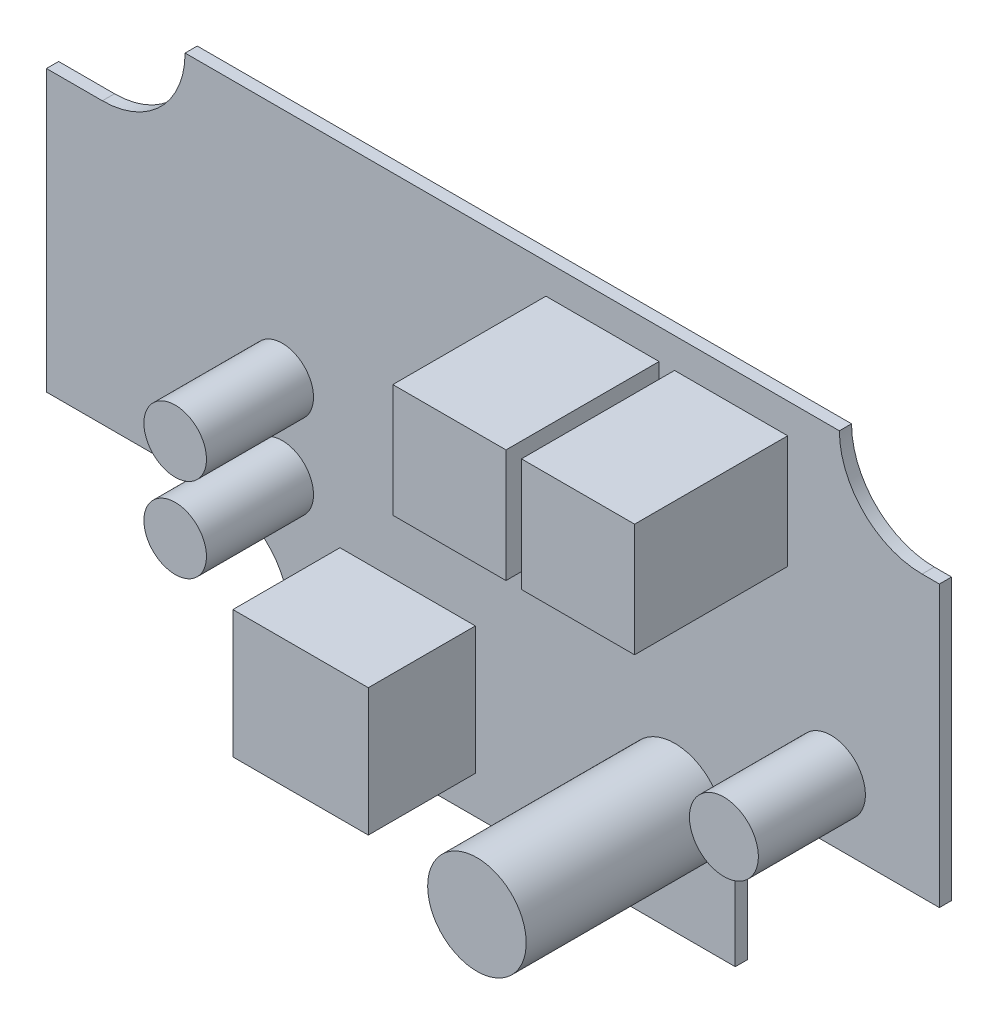
SolidWorks part; units mm, degrees
ref_plane "Front Plane" through (0, 0, 0) normal (0, 0, 1) x (1, 0, 0)
ref_plane "Top Plane" through (0, 0, 0) normal (0, 1, 0) x (1, 0, 0)
ref_plane "Right Plane" through (0, 0, 0) normal (1, 0, 0) x (0, 0, -1)
sketch "Sketch1" plane through (0, 0, 0) normal (0, 0, 1) x (1, 0, 0)
  line L0 (-42.3541, 30.2967) -> (-53.0616, 30.2967) construction
  line L1 (28.8728, -26.0779) -> (28.8728, -36.5363)
  line L2 (-38.257, -16.6937) -> (-60.3013, -16.6937)
  line L3 (-42.3541, 30.2967) -> (42.3541, 30.2967)
  line L4 (38.257, -16.6937) -> (55.3008, -16.6937)
  line L5 (-53.0616, 30.2967) -> (-53.0616, 19.5893) construction
  line L6 (-38.257, -16.6937) -> (-38.257, -26.0779) construction
  line L7 (-38.257, -26.0779) -> (-28.8728, -26.0779) construction
  line L8 (28.8728, -26.0779) -> (38.257, -26.0779) construction
  line L9 (38.257, -26.0779) -> (38.257, -16.6937) construction
  line L10 (53.0616, 19.5893) -> (53.0616, 30.2967) construction
  line L11 (53.0616, 30.2967) -> (42.3541, 30.2967) construction
  line L12 (55.3008, -16.6937) -> (55.3008, 19.5893)
  line L13 (-60.3013, -16.6937) -> (-60.3013, 19.5893)
  line L14 (-60.3013, 19.5893) -> (-53.0616, 19.5893)
  line L15 (55.3008, 19.5893) -> (53.0616, 19.5893)
  line L16 (28.8728, -36.5363) -> (-28.8728, -36.5363)
  line L17 (-28.8728, -36.5363) -> (-28.8728, -26.0779)
  line L21 (0, -36.5363) -> (0, 0) construction
  arc A0 (-42.3541, 30.2967) -> (-53.0616, 19.5893) centre (-53.0616, 30.2967) cw
  arc A2 (-38.257, -16.6937) -> (-28.8728, -26.0779) centre (-38.257, -26.0779) cw
  arc A4 (42.3541, 30.2967) -> (53.0616, 19.5893) centre (53.0616, 30.2967) ccw
  arc A5 (38.257, -16.6937) -> (28.8728, -26.0779) centre (38.257, -26.0779) ccw
  dimension "D1" = 36.2829
  dimension "D2" = 9.3842
  dimension "D3" = 10.7075
  dimension "D4" = 57.7457
  dimension "D5" = 22.0442
  dimension "D6" = 10.4584
  dimension "D7" = 17.0438
  dimension "D8" = 2.2392
extrude "Boss-Extrude1" add sketch "Sketch1" along normal blind 1.5748
sketch "Sketch2" plane through (0, 0, 1.5748) normal (0, 0, 1) x (1, 0, 0)
  line L1 (4.3619, 26.3914) -> (19.0119, 26.3914)
  line L2 (4.3619, 26.3914) -> (4.3619, 11.7414)
  line L3 (4.3619, 11.7414) -> (19.0119, 11.7414)
  line L4 (19.0119, 26.3914) -> (19.0119, 11.7414)
  line L5 (21.0119, 26.3914) -> (35.6619, 26.3914)
  line L6 (21.0119, 26.3914) -> (21.0119, 11.7414)
  line L7 (21.0119, 11.7414) -> (35.6619, 11.7414)
  line L8 (35.6619, 26.3914) -> (35.6619, 11.7414)
  dimension "D1" = 2
  dimension "D2" = 14.65
extrude "Boss-Extrude2" add sketch "Sketch2" along normal blind 19.82
sketch "Sketch3" plane through (0, 0, 1.5748) normal (0, 0, 1) x (1, 0, 0)
  circle A0 centre (21.0509, -21.7791) radius 6.38
  dimension "D1" = 12.76
extrude "Boss-Extrude3" add sketch "Sketch3" along normal blind 25.62
sketch "Sketch4" plane through (0, 0, 1.5748) normal (0, 0, 1) x (1, 0, 0)
  line L1 (-22.3027, -15.1438) -> (-4.7739, -15.1438)
  line L2 (-22.3027, -15.1438) -> (-22.3027, -31.671)
  line L3 (-22.3027, -31.671) -> (-4.7739, -31.671)
  line L4 (-4.7739, -15.1438) -> (-4.7739, -31.671)
  circle A0 centre (-29.7754, 0) radius 4.05
  circle A1 centre (-29.7754, -10.91) radius 4.05
  circle A2 centre (41.2613, -8.8411) radius 4.4585
  dimension "D1" = 8.1
  dimension "D2" = 16.5272
  dimension "D4" = 8.9169
  dimension "D3" = 17.5288
extrude "Boss-Extrude4" add sketch "Sketch4" along normal blind 13.86
